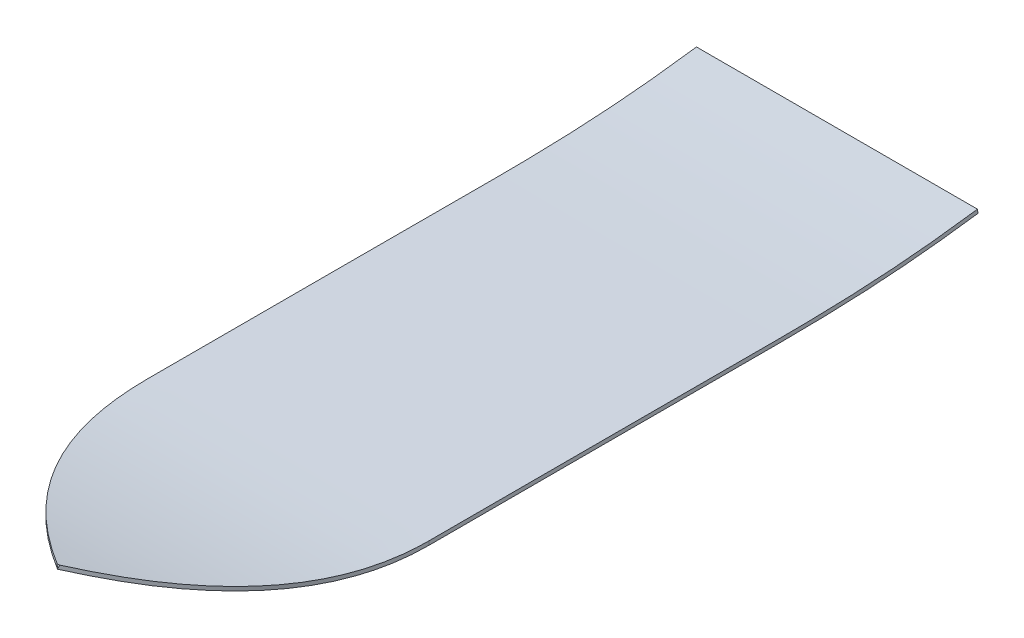
SolidWorks part; units mm, degrees
ref_plane "Front Plane" through (0, 0, 0) normal (0, 0, 1) x (1, 0, 0)
ref_plane "Top Plane" through (0, 0, 0) normal (0, 1, 0) x (1, 0, 0)
ref_plane "Right Plane" through (0, 0, 0) normal (1, 0, 0) x (0, 0, -1)
sketch "Sketch1" plane through (0, 0, 0) normal (1, 0, 0) x (0, 0, -1)
  line L14 (-2353.491, -376.5846) -> (-2348.0397, -352.1862)
  line L15 (2643.1252, -450.6172) -> (2639.843, -425.8336)
  spline S0 degree 3 poles (-2348.0397, -352.1862) (-2281.6739, -367.014) (-2145.0366, -397.3545) (-1955.2566, -429.8841) (-1782.2899, -454.4244) (-1631.3594, -471.9968) (-1477.832, -486.206) (-1315.1813, -497.4765) (-1143.0182, -505.3042) (-1011.5074, -508.0818) (-929.7205, -508.681) (-905.794, -508.7625) (-888.669, -508.7758) (-868.1018, -508.7696) (-768.7074, -508.7573) (-590.4822, -508.7341) (-316.2882, -508.6967) (-14.6749, -508.6557) (314.3578, -508.611) (677.6647, -508.5616) (951.8586, -508.5229) (1124.9436, -508.5038) (1155.7894, -508.5121) (1167.7871, -508.486) (1176.3478, -508.5873) (1197.69, -508.7611) (1294.258, -509.4498) (1408.7224, -509.4433) (1531.6873, -508.1187) (1606.7968, -506.846) (1681.02, -505.0933) (1754.5207, -502.8324) (1827.4611, -500.0365) (1924.191, -495.5547) (2044.4927, -488.4923) (2213.5079, -475.4909) (2408.6679, -456.4495) (2562.7846, -436.0389) (2639.843, -425.8336) knots 0.002527 0.002527 0.002527 0.002527 0.046875 0.09375 0.125 0.15625 0.1875 0.21875 0.253906 0.289062 0.294922 0.300781 0.302734 0.304688 0.3125 0.359375 0.40625 0.46875 0.53125 0.59375 0.675781 0.6875 0.692383 0.693359 0.694336 0.697266 0.705566 0.75 0.765625 0.78125 0.796875 0.8125 0.828125 0.84375 0.875 0.90625 0.953125 1 1 1 1
  spline S1 degree 1 poles (-2353.491, -376.5846) (2643.1252, -450.6172) knots 0 0 1 1 construction
  spline S2 degree 3 poles (-2353.491, -376.5846) (-2341.8172, -379.1928) (-2318.4832, -384.4007) (-2271.677, -394.7545) (-2212.903, -407.4554) (-2141.5999, -421.9472) (-2069.4633, -435.3507) (-1996.6444, -447.7907) (-1898.7422, -463.2254) (-1774.8533, -480.5832) (-1623.5137, -497.9412) (-1469.6253, -511.9427) (-1313.1406, -522.5549) (-1180.5878, -528.5836) (-1073.2523, -531.7166) (-1005.6315, -532.9712) (-951.2075, -533.5521) (-917.068, -533.7407) (-889.6479, -533.7805) (-862.2872, -533.7657) (-828.1073, -533.7657) (-787.08, -533.7592) (-732.3809, -533.7526) (-636.6555, -533.7399) (-499.9054, -533.7218) (-335.8047, -533.6994) (-171.7041, -533.6771) (-7.6035, -533.6548) (156.4971, -533.6325) (320.5976, -533.6101) (484.6982, -533.5878) (648.7989, -533.5653) (785.5493, -533.5463) (894.9496, -533.5316) (963.3247, -533.5228) (1018.0248, -533.516) (1059.0497, -533.5113) (1093.2376, -533.5069) (1117.1653, -533.5062) (1130.8384, -533.507) (1141.0903, -533.5088) (1149.648, -533.5094) (1156.5035, -533.505) (1160.7909, -533.5002) (1164.2253, -533.4933) (1166.6969, -533.4918) (1169.0741, -533.5049) (1171.5732, -533.5317) (1174.1652, -533.5603) (1177.5983, -533.5944) (1183.5963, -533.6479) (1192.1021, -533.714) (1205.6801, -533.8172) (1229.3492, -533.9815) (1262.9077, -534.1651) (1316.0673, -534.339) (1381.5733, -534.326) (1458.8309, -533.9133) (1534.9014, -533.0763) (1634.9616, -531.3571) (1757.8765, -528.0092) (1903.2117, -521.8441) (2047.653, -513.3339) (2168.4343, -504.0249) (2265.6637, -495.3245) (2339.2509, -488.037) (2413.8364, -479.8551) (2489.6647, -470.6592) (2566.2261, -460.8015) (2617.5149, -454.009) (2643.1252, -450.6172) knots 0.002527 0.002527 0.002527 0.002527 0.01032 0.018113 0.033698 0.049284 0.064869 0.080455 0.09604 0.127211 0.158382 0.189553 0.220724 0.251895 0.267481 0.283066 0.290859 0.298652 0.302548 0.306445 0.314237 0.32203 0.329823 0.345408 0.376579 0.407751 0.438922 0.470093 0.501264 0.532435 0.563606 0.594777 0.625948 0.641533 0.657119 0.664911 0.672704 0.680497 0.684393 0.686342 0.68829 0.690238 0.691212 0.692186 0.692673 0.69316 0.693647 0.694134 0.694621 0.695108 0.696083 0.698031 0.699979 0.703875 0.711668 0.719461 0.735046 0.750632 0.766217 0.781803 0.812974 0.844145 0.875316 0.906487 0.922072 0.937658 0.953243 0.968829 0.984414 1 1 1 1
  dimension "D1" = 25
extrude "Boss-Extrude1" add sketch "Sketch1" along normal blind 1524 and the other way blind 1524
sketch "Sketch3" plane through (0, 0, 0) normal (0, 1, 0) x (1, 0, 0)
  line L0 (-900, 2643.745) -> (900, 2643.745)
  line L1 (-900, 2643.745) -> (-900, -873.7886)
  line L2 (900, 2643.745) -> (900, -873.7886)
  line L3 (0, 2955.5244) -> (0, -2061.9995) construction
  line L4 (-2934.2017, 4085.2419) -> (2797.2556, 4085.2419)
  line L5 (-2934.2017, 4085.2419) -> (-2934.2017, -3918.064)
  line L6 (-2934.2017, -3918.064) -> (2797.2556, -3918.064)
  line L7 (2797.2556, 4085.2419) -> (2797.2556, -3918.064)
  line L8 (-94.9374, 0) -> (0, 0) construction
  line L9 (-1524, -2353.491) -> (1524, -2353.491) construction
  line L11 (-1524, 1954.9582) -> (1524, 1954.9582) construction
  spline S0 degree 2 poles (-900, -873.7886) (-900, -1748.4272) (0, -2353.491) knots 0 0 0 1 1 1
  spline S1 degree 2 poles (900, -873.7886) (900, -1748.4272) (0, -2353.491) knots 0 0 0 1 1 1
  point P13 (0, 0)
  point P14 (0, -2353.491)
  dimension "D1" = 1800
extrude "Cut-Extrude1" cut sketch "Sketch3" against normal through all both and the other way through all
